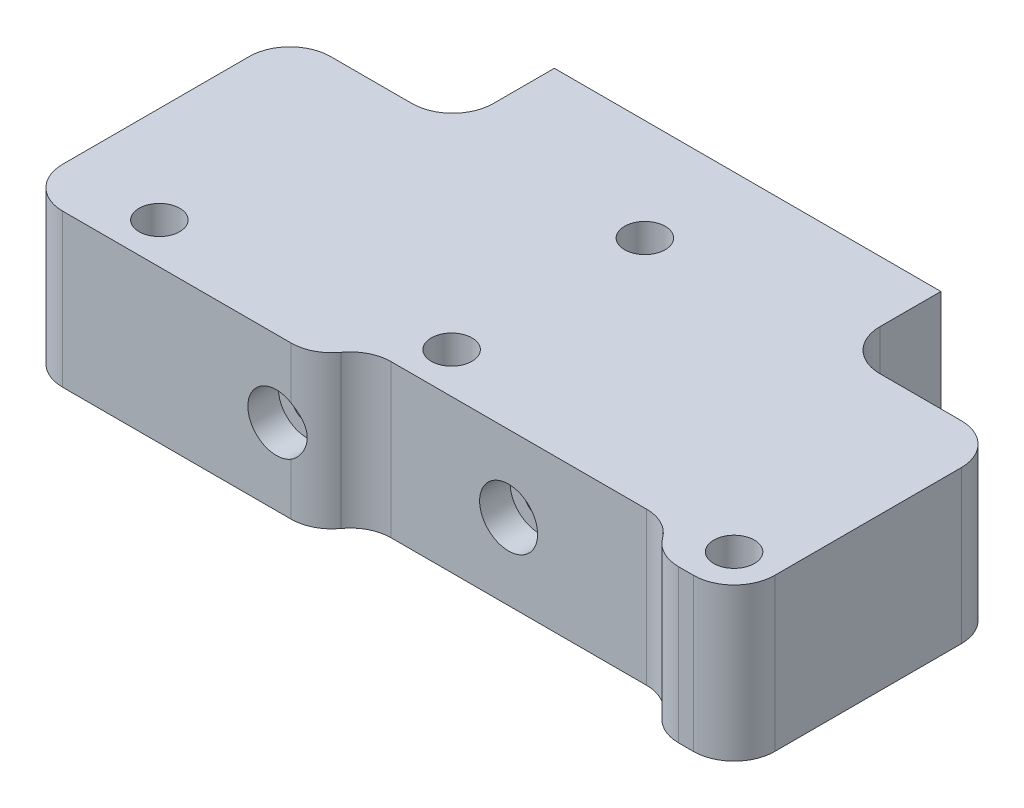
SolidWorks part; units mm, degrees
ref_plane "Front Plane" through (0, 0, 0) normal (0, 0, 1) x (1, 0, 0)
ref_plane "Top Plane" through (0, 0, 0) normal (0, 1, 0) x (1, 0, 0)
ref_plane "Right Plane" through (0, 0, 0) normal (1, 0, 0) x (0, 0, -1)
sketch "Sketch1" plane through (0, 0, 0) normal (0, 1, 0) x (1, 0, 0)
  line L1 (0, 0) -> (-70, 0)
  line L2 (0, 0) -> (0, 34)
  line L3 (0, 34) -> (-70, 34)
  line L4 (-70, 0) -> (-70, 34)
  circle A0 centre (-35.1, 24) radius 2
  circle A1 centre (-35.1, 5) radius 2
  dimension "D5" = 4
  dimension "D6" = 4
  dimension "D7" = 34.9
  dimension "D8" = 34.9
  dimension "D1" = 34
  dimension "D2" = 70
  dimension "D3" = 10
  dimension "D4" = 5
extrude "Boss-Extrude1" add sketch "Sketch1" along normal blind 15
sketch "Sketch4" plane through (0, 0, -34) normal (0, 0, -1) x (-1, 0, 0)
  line L0 (0, 15) -> (70, 15) construction
  line L1 (0, 15) -> (0, 0) construction
  line L2 (70, 15) -> (70, 0) construction
  circle A0 centre (7.5, 10.15) radius 2.5
  circle A1 centre (62.5, 10.15) radius 2.5
  dimension "D3" = 5
  dimension "D5" = 7.5
  dimension "D6" = 5
  dimension "D1" = 4.85
  dimension "D2" = 7.5
  dimension "D4" = 4.85
sketch "Sketch5" plane through (0, 0, 0) normal (0, 0, 1) x (1, 0, 0)
  line L0 (-70, 0) -> (0, 0) construction
  line L1 (-70, 15) -> (-70, 0) construction
  line L2 (0, 15) -> (0, 0) construction
  line L3 (-70, 15) -> (0, 15) construction
  circle A0 centre (-62.5, 10.15) radius 4.3
  circle A1 centre (-7.5, 10.15) radius 4.3
  dimension "D1" = 8.6
  dimension "D3" = 7.5
  dimension "D4" = 7.5
  dimension "D5" = 4.85
  dimension "D6" = 8.6
  dimension "D2" = 10.15
sketch "Sketch6" plane through (0, 0, 0) normal (0, 0, 1) x (1, 0, 0)
  line L4 (-70, 0) -> (0, 0)
  line L5 (0, 0) -> (0, 15)
  line L6 (0, 15) -> (-70, 15)
  line L7 (-70, 15) -> (-70, 0)
  line L8 (-70, 0) -> (0, 0)
  line L9 (0, 0) -> (0, 15)
  line L10 (0, 15) -> (-70, 15)
  line L11 (-70, 15) -> (-70, 0)
  dimension "D1" = 0
extrude "Boss-Extrude2" add sketch "Sketch6" along normal blind 5 contours L8 L9 L10 L11
sketch "Sketch3" plane through (0, 15, 0) normal (0, 1, 0) x (1, 0, 0)
  line L0 (0, -5) -> (0, 34) construction
  line L3 (56.0549, 7.6668) -> (-275.4464, 7.6668) construction
  line L4 (0, -5) -> (-70, -5) construction
  circle A0 centre (-4, 1.67) radius 2
  circle A1 centre (-60.5, 1.67) radius 2
  circle A2 centre (-4, 1.67) radius 6 construction
  dimension "D1" = 4
  dimension "D2" = 4
  dimension "D3" = 6.67
  dimension "D4" = 4
  dimension "D5" = 6.67
  dimension "D6" = 56.5
  dimension "D7" = 4
extrude "Cut-Extrude2" cut sketch "Sketch3" against normal blind 15
sketch "Sketch8" plane through (0, 15, 0) normal (0, 1, 0) x (1, 0, 0)
  line L0 (-19.5, -5) -> (-19.5, 0)
  line L1 (0, -5) -> (-70, -5) construction
  line L2 (-19.5, 0) -> (-13.5, 0)
  line L3 (-13.5, -5) -> (-13.5, 0)
  line L4 (-13.5, -5) -> (-19.5, -5)
  line L5 (0, -5) -> (0, 34) construction
  dimension "D1" = 6
  dimension "D2" = 5
  dimension "D3" = 13.5
extrude "Cut-Extrude3" cut sketch "Sketch8" against normal blind 15
sketch "Sketch9" plane through (0, 15, 0) normal (0, 1, 0) x (1, 0, 0)
  line L0 (-19.5, -5) -> (-70, -5) construction
  line L1 (-29, -5) -> (-41, -5)
  line L2 (-29, -5) -> (-29, 1)
  line L3 (-29, 1) -> (-41, 1)
  line L4 (-41, -5) -> (-41, 1)
  line L5 (-35, 1) -> (-35, 34) construction
  line L6 (0, 34) -> (-70, 34) construction
  dimension "D1" = 12
  dimension "D2" = 6
extrude "Cut-Extrude4" cut sketch "Sketch9" against normal blind 15
sketch "Sketch10" plane through (0, 0, 0) normal (0, -1, 0) x (1, 0, 0)
  line L0 (0, -34) -> (-70, -34) construction
  line L1 (0, -34) -> (-16, -34)
  line L2 (0, -34) -> (0, -24)
  line L3 (0, -24) -> (-16, -24)
  line L4 (-16, -34) -> (-16, -24)
  line L5 (0, 5) -> (0, -34) construction
  line L6 (-35, -34) -> (-35, -1) construction
  line L7 (-29, -1) -> (-41, -1) construction
  line L8 (-70, -34) -> (-54, -34)
  line L9 (-70, -34) -> (-70, -24)
  line L10 (-54, -34) -> (-54, -24)
  line L11 (-70, -24) -> (-54, -24)
  dimension "D1" = 16
  dimension "D2" = 10
extrude "Cut-Extrude5" cut sketch "Sketch10" against normal blind 17
sketch "Sketch12" plane through (0, 0, 5) normal (0, 0, 1) x (1, 0, 0)
  line L0 (-45, 0) -> (-45, 15) construction
  line L1 (-41, 15) -> (-70, 15) construction
  line L2 (-41, 0) -> (-41, 15) construction
  line L3 (-70, 0) -> (-41, 0) construction
  line L4 (-25.5, 7.5) -> (-25.5, 0) construction
  line L7 (-16, 0) -> (-54, 0) construction
  line L8 (0, 15) -> (0, 0) construction
  circle A0 centre (-45, 7.5) radius 1.5
  circle A2 centre (-25.5, 7.5) radius 1.5
  dimension "D2" = 3
  dimension "D3" = 25.5
  dimension "D1" = 4
  dimension "D4" = 7.5
extrude "Cut-Extrude6" cut sketch "Sketch12" against normal blind 41
sketch "Sketch13" plane through (0, 15, 0) normal (0, 1, 0) x (1, 0, 0)
  line L0 (-13.5, -5) -> (-13.5, 0) construction
  line L1 (-13.5, -5) -> (-41, -5)
  line L2 (-13.5, -5) -> (-13.5, 1)
  line L3 (-13.5, 1) -> (-41, 1)
  line L4 (-41, -5) -> (-41, 1)
  line L5 (-41, 1) -> (-41, -5) construction
  line L6 (-16, 34) -> (-54, 34) construction
  dimension "D1" = 6
  dimension "D2" = 33
extrude "Cut-Extrude7" cut sketch "Sketch13" against normal blind 20
sketch "Sketch14" plane through (0, 0, 0) normal (0, -1, 0) x (-1, 0, 0)
  line L0 (0, -5) -> (0, 24) construction
  line L1 (0, -5) -> (13.5, -5)
  line L2 (0, -5) -> (0, -2.33)
  line L3 (0, -2.33) -> (13.5, -2.33)
  line L4 (13.5, -5) -> (13.5, -2.33)
  line L5 (13.5, -5) -> (13.5, 1) construction
  line L6 (0, 24) -> (16, 24) construction
  line L7 (70, -5) -> (41, -5) construction
  line L8 (70, -5) -> (41, -5)
  line L9 (70, -5) -> (70, -2.33)
  line L10 (70, -2.33) -> (41, -2.33)
  line L11 (41, -5) -> (41, -2.33)
  line L12 (70, 24) -> (70, -5) construction
  line L13 (41, 1) -> (41, -5) construction
  circle A0 centre (4.5, 1.67) radius 2 construction
  dimension "D1" = 4
  dimension "D3" = 22.33
  dimension "D4" = 4
  dimension "D2" = 4.5
  dimension "D5" = 2.67
  dimension "D6" = 2.67
extrude "Cut-Extrude8" cut sketch "Sketch14" against normal blind 17
fillet "Fillet2" radius 4 4 edges at (-70, 7.5, -24) (0, 7.5, -24) (0, 7.5, 2.33) (-70, 7.5, 2.33)
sketch "Sketch16" plane through (0, 0, 0) normal (0, -1, 0) x (1, 0, 0)
  line L0 (-13.5, 2.33) -> (-13.5, -1) construction
  line L1 (-13.5, 2.33) -> (-8, 2.33)
  line L2 (-13.5, 2.33) -> (-13.5, -1)
  line L3 (-13.5, -1) -> (-8, -1)
  line L4 (-8, 2.33) -> (-8, -1)
  line L5 (-13.5, 2.33) -> (-4, 2.33) construction
  circle A0 centre (-4, -1.67) radius 2 construction
  dimension "D1" = 4
  dimension "D2" = 3.33
extrude "Cut-Extrude10" cut sketch "Sketch16" against normal blind 18
fillet "Fillet4" radius 4 4 edges at (-16, 7.5, -24) (-54, 7.5, -24) (-41, 7.5, -1) (-8, 7.5, -1)
fillet "Fillet5" radius 4 2 edges at (-41, 7.5, 2.33) (-8, 7.5, 2.33)
sketch "Sketch17" plane through (0, 0, -1) normal (0, 0, 1) x (1, 0, 0)
  line L0 (-11.9435, 0) -> (-37.0565, 0) construction
  line L1 (-11.9435, 0) -> (-11.9435, 15) construction
  circle A0 centre (-25.5, 7.5) radius 2.85
  dimension "D1" = 5.7
  dimension "D2" = 7.5
  dimension "D3" = 13.5565
extrude "Cut-Extrude11" cut sketch "Sketch17" against normal blind 3
sketch "Sketch18" plane through (0, 0, 2.33) normal (0, 0, 1) x (1, 0, 0)
  line L0 (-66, 0) -> (-43.552, 0) construction
  line L1 (-66, 15) -> (-66, 0) construction
  circle A0 centre (-45, 7.5) radius 2.8
  dimension "D1" = 5.6
  dimension "D2" = 7.5
  dimension "D3" = 21
extrude "Cut-Extrude12" cut sketch "Sketch18" against normal blind 3
chamfer "Chamfer1" distance 2 angle 45 1 edges at (-35.1, 0, -22)
chamfer "Chamfer2" distance 2 angle 45 1 edges at (-35.1, 0, -3)
